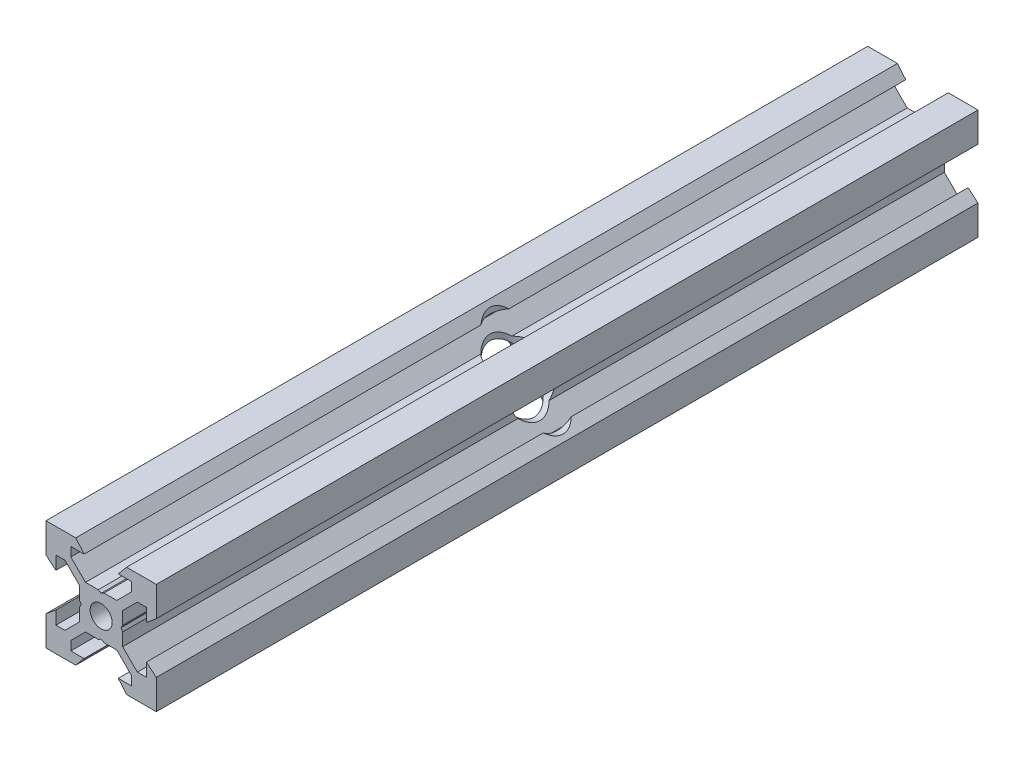
SolidWorks part; units mm, degrees
material "3.3535 (EN-AW 5754)"
ref_plane "Front Plane" through (0, 0, 0) normal (0, 0, 1) x (1, 0, 0)
ref_plane "Top Plane" through (0, 0, 0) normal (0, 1, 0) x (1, 0, 0)
ref_plane "Right Plane" through (0, 0, 0) normal (1, 0, 0) x (0, 0, -1)
sketch "Sketch1" plane through (0, 0, 0) normal (0, 0, 1) x (1, 0, 0)
  line L0 (10, 10) -> (4.6104, 10) construction
  line L1 (10, 10) -> (10, 4.6104) construction
  line L2 (10, -10) -> (10, -4.6104) construction
  line L3 (10, -10) -> (4.6104, -10) construction
  line L4 (10, 10) -> (10, 4.6104)
  line L5 (6.5607, 5.5) -> (8.2, 5.5)
  line L6 (5.5, 8.2) -> (5.5, 6.5607)
  line L7 (10, 10) -> (4.6104, 10)
  line L8 (10, 10) -> (10, 4.6104)
  line L9 (6.5607, 5.5) -> (3.9, 2.8393)
  line L10 (5.5, 6.5607) -> (2.8393, 3.9)
  line L11 (10, 4.6104) -> (8.2, 3.1)
  line L12 (4.6104, 10) -> (3.1, 8.2)
  line L13 (8.2, 3.1) -> (8.2, 5.5)
  line L14 (3.1, 8.2) -> (5.5, 8.2)
  line L15 (-6.5607, 5.5) -> (-8.2, 5.5)
  line L16 (6.5607, -5.5) -> (8.2, -5.5)
  line L17 (3.1, -8.2) -> (5.5, -8.2)
  line L18 (8.2, -3.1) -> (8.2, -5.5)
  line L19 (4.6104, -10) -> (3.1, -8.2)
  line L20 (10, -4.6104) -> (8.2, -3.1)
  line L21 (0.5196, -3.9) -> (0, -3.6)
  line L22 (0.5196, 3.9) -> (0, 3.6)
  line L23 (3.6, 0) -> (3.9, -0.5196)
  line L24 (3.9, 0.5196) -> (3.6, 0)
  line L25 (3.9, 0.5196) -> (3.9, 2.8393)
  line L26 (2.8393, 3.9) -> (0.5196, 3.9)
  line L27 (3.9, -2.8393) -> (3.9, -0.5196)
  line L28 (2.8393, -3.9) -> (0.5196, -3.9)
  line L29 (5.5, -6.5607) -> (2.8393, -3.9)
  line L30 (6.5607, -5.5) -> (3.9, -2.8393)
  line L31 (10, -10) -> (10, -4.6104)
  line L32 (10, -10) -> (4.6104, -10)
  line L33 (5.5, -8.2) -> (5.5, -6.5607)
  line L34 (-6.5607, -5.5) -> (-8.2, -5.5)
  line L35 (10, -10) -> (10, -4.6104)
  line L36 (0, 0) -> (0, 8.2) construction
  line L37 (-10, -10) -> (-4.6104, -10) construction
  line L38 (-10, -10) -> (-10, -4.6104) construction
  line L39 (-10, 10) -> (-10, 4.6104) construction
  line L40 (-10, 10) -> (-4.6104, 10) construction
  line L41 (-10, -10) -> (-10, -4.6104)
  line L43 (-5.5, -8.2) -> (-5.5, -6.5607)
  line L44 (-10, -10) -> (-4.6104, -10)
  line L45 (-10, -10) -> (-10, -4.6104)
  line L46 (-6.5607, -5.5) -> (-3.9, -2.8393)
  line L47 (-5.5, -6.5607) -> (-2.8393, -3.9)
  line L48 (-2.8393, -3.9) -> (-0.5196, -3.9)
  line L49 (-3.9, -2.8393) -> (-3.9, -0.5196)
  line L50 (-2.8393, 3.9) -> (-0.5196, 3.9)
  line L51 (-3.9, 0.5196) -> (-3.9, 2.8393)
  line L52 (-3.9, 0.5196) -> (-3.6, 0)
  line L53 (-3.6, 0) -> (-3.9, -0.5196)
  line L54 (-0.5196, 3.9) -> (0, 3.6)
  line L55 (-0.5196, -3.9) -> (0, -3.6)
  line L56 (-10, -4.6104) -> (-8.2, -3.1)
  line L57 (-4.6104, -10) -> (-3.1, -8.2)
  line L58 (-8.2, -3.1) -> (-8.2, -5.5)
  line L59 (-3.1, -8.2) -> (-5.5, -8.2)
  line L60 (-10, -10) -> (10, -10) construction
  line L61 (-10, -10) -> (-10, 10) construction
  line L62 (-3.1, 8.2) -> (-5.5, 8.2)
  line L63 (-8.2, 3.1) -> (-8.2, 5.5)
  line L64 (-4.6104, 10) -> (-3.1, 8.2)
  line L65 (-10, 4.6104) -> (-8.2, 3.1)
  line L66 (-5.5, 6.5607) -> (-2.8393, 3.9)
  line L67 (-6.5607, 5.5) -> (-3.9, 2.8393)
  line L68 (-10, 10) -> (-10, 4.6104)
  line L69 (-10, 10) -> (-4.6104, 10)
  line L70 (-5.5, 8.2) -> (-5.5, 6.5607)
  line L71 (-10, 10) -> (10, 10) construction
  line L72 (-10, 10) -> (-10, 4.6104)
  line L73 (10, -10) -> (10, 10) construction
  line L74 (-10, -10) -> (10, 10) construction
  line L75 (-10, 10) -> (10, -10) construction
  circle A0 centre (0, 0) radius 2
  dimension "D7" = 4
  dimension "D1" = 20
  dimension "D2" = 5.3896
  dimension "D3" = 4.5
  dimension "D4" = 50
  dimension "D5" = 1.8
  dimension "D6" = 1.5104
  dimension "D8" = 5.5
  dimension "D9" = 120
  dimension "D10" = 0.3
  dimension "D11" = 2.3197
  dimension "D12" = 7.8
  dimension "D13" = 7.8
  dimension "D14" = 1.5
  dimension "D15" = 2.6607
extrude "Boss-Extrude1" add sketch "Sketch1" along normal blind 149 contours L70 L62 L64 L69 L68 L65 L63 L15 L67 L51 L52 L53 L49 L46 L34 L58 L56 L41 L44 L57 L59 L43 L47 L48 L55 L21 L28 L29 L33 L17 L19 L32 L31 L20 L18 L16 L30 L27 L23 L24 L25 L9 L5 L13 L11 L4 L7 L12 L14 L6 L10 region at (9.7172, 7.3052, 0)
sketch "Sketch4" plane through (0, 0, 0) normal (1, 0, 0) x (0, 0, -1)
  line L0 (-149, 0) -> (0, 0) construction
  circle A0 centre (-74.5, 0) radius 4
  dimension "D1" = 8
extrude "Cut-Extrude1" cut sketch "Sketch4" against normal through all both and the other way through all
sketch "Sketch5" plane through (0, 0, 0) normal (0, 1, 0) x (1, 0, 0)
  line L0 (0, 0) -> (0, -149) construction
  circle A0 centre (0, -74.5) radius 4
  dimension "D1" = 8
extrude "Cut-Extrude2" cut sketch "Sketch5" against normal through all both and the other way through all
